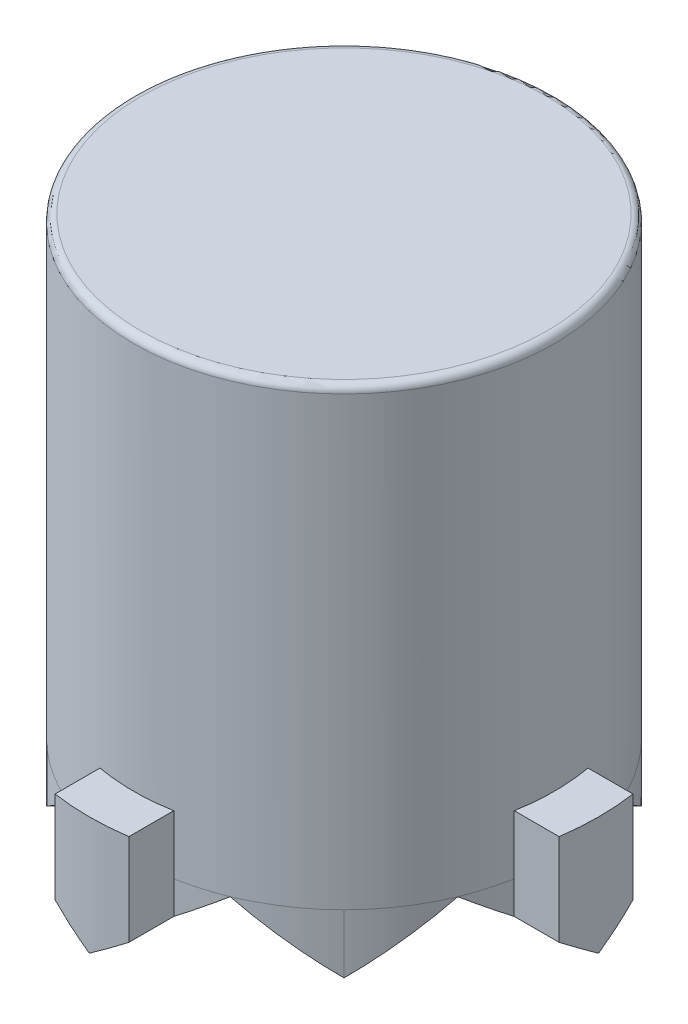
SolidWorks part; units mm, degrees
note: The reader was unsure of these and kept them because the rebuilt part matched: shared geometry of "Croquis22<3>", "Croquis26<2>", "Croquis28<2>", "Croquis29<2>".
ref_plane "Front Plane" through (0, 0, 0) normal (0, 0, 1) x (1, 0, 0)
ref_plane "Top Plane" through (0, 0, 0) normal (0, 1, 0) x (1, 0, 0)
ref_plane "Right Plane" through (0, 0, 0) normal (1, 0, 0) x (0, 0, -1)
sketch "Croquis1" plane through (0, 0, 0) normal (0, 1, 0) x (1, 0, 0)
  circle A0 centre (0, 0) radius 2.85
  dimension "D1" = 5.7
extrude "Saliente-Extruir1" add sketch "Croquis1" along normal blind 6.95
fillet "Redondeo1" radius 0.1 1 edges at (0, 6.95, 2.85)
sketch "Croquis3" plane through (0, 0, 0) normal (0, -1, 0) x (1, 0, 0)
  circle A0 centre (0, 0) radius 2.25
  dimension "D1" = 4.5
extrude "Cortar-Extruir1" cut sketch "Croquis3" against normal blind 4
sketch "Croquis4" plane through (0, 0, 0) normal (0, -1, 0) x (1, 0, 0)
  circle A0 centre (0, 0) radius 2.55
  dimension "D1" = 5.1
curve "Hélice/Espiral1" pitch 12.8 height 0.8 turns 0.0625
sketch "Croquis5" plane through (0, 0, 0) normal (0, -1, 0) x (1, 0, 0)
  circle A1 centre (0, 0) radius 2.55
  circle A2 centre (0, 0) radius 2.55
  dimension "D1" = 0
curve "Hélice/Espiral2" pitch 12.8 height 0.8 turns 0.0625
sketch "Croquis6" plane through (0, 0, 0) normal (0, -1, 0) x (1, 0, 0)
  circle A1 centre (0, 0) radius 2.55
  circle A2 centre (0, 0) radius 2.55
  dimension "D1" = 0
curve "Hélice/Espiral3" pitch 12.8 height 0.8 turns 0.0625
sketch "Croquis7" plane through (0, 0, 0) normal (0, -1, 0) x (1, 0, 0)
  circle A1 centre (0, 0) radius 2.55
  circle A2 centre (0, 0) radius 2.55
  dimension "D1" = 0
curve "Hélice/Espiral4" pitch 12.8 height 0.8 turns 0.0625
sketch "Croquis8" plane through (0, 0, 0) normal (0, -1, 0) x (1, 0, 0)
  circle A1 centre (0, 0) radius 2.55
  circle A2 centre (0, 0) radius 2.55
  dimension "D1" = 0
curve "Hélice/Espiral5" pitch 12.8 height 0.8 turns 0.0625
sketch "Croquis9" plane through (0, 0, 0) normal (0, -1, 0) x (1, 0, 0)
  circle A1 centre (0, 0) radius 2.55
  circle A2 centre (0, 0) radius 2.55
  dimension "D1" = 0
curve "Hélice/Espiral6" pitch 12.8 height 0.8 turns 0.0625
sketch "Croquis10" plane through (0, 0, 0) normal (0, -1, 0) x (1, 0, 0)
  circle A1 centre (0, 0) radius 2.55
  circle A2 centre (0, 0) radius 2.55
  dimension "D1" = 0
curve "Hélice/Espiral7" pitch 12.8 height 0.8 turns 0.0625
sketch "Croquis11" plane through (0, 0, 0) normal (0, -1, 0) x (1, 0, 0)
  circle A1 centre (0, 0) radius 2.55
  circle A2 centre (0, 0) radius 2.55
  dimension "D1" = 0
curve "Hélice/Espiral8" pitch 12.8 height 0.8 turns 0.0625
sketch "Croquis12" plane through (0, 0, 0) normal (0, -1, 0) x (1, 0, 0)
  circle A3 centre (0, 0) radius 2.55
  circle A4 centre (0, 0) radius 2.55
  dimension "D2" = 0
curve "Hélice/Espiral9" pitch 12.8 height 0.8 turns 0.0625
sketch "Croquis13" plane through (0, 0, 0) normal (0, -1, 0) x (1, 0, 0)
  circle A1 centre (0, 0) radius 2.55
  circle A2 centre (0, 0) radius 2.55
  dimension "D1" = 0
curve "Hélice/Espiral10" pitch 12.8 height 0.8 turns 0.0625
sketch "Croquis14" plane through (0, 0, 0) normal (0, -1, 0) x (1, 0, 0)
  circle A1 centre (0, 0) radius 2.55
  circle A2 centre (0, 0) radius 2.55
  dimension "D1" = 0
curve "Hélice/Espiral11" pitch 12.8 height 0.8 turns 0.0625
sketch "Croquis15" plane through (0, 0, 0) normal (0, -1, 0) x (1, 0, 0)
  circle A1 centre (0, 0) radius 2.55
  circle A2 centre (0, 0) radius 2.55
  dimension "D1" = 0
curve "Hélice/Espiral12" pitch 12.8 height 0.8 turns 0.0625
sketch "Croquis16" plane through (0, 0, 0) normal (0, -1, 0) x (1, 0, 0)
  circle A1 centre (0, 0) radius 2.55
  circle A2 centre (0, 0) radius 2.55
  dimension "D1" = 0
curve "Hélice/Espiral13" pitch 12.8 height 0.8 turns 0.0625
sketch "Croquis17" plane through (0, 0, 0) normal (0, -1, 0) x (1, 0, 0)
  circle A1 centre (0, 0) radius 2.55
  circle A2 centre (0, 0) radius 2.55
  dimension "D1" = 0
curve "Hélice/Espiral15" pitch 12.8 height 0.8 turns 0.0625
sketch "Croquis18" plane through (0, 0, 0) normal (0, -1, 0) x (1, 0, 0)
  circle A1 centre (0, 0) radius 2.55
  circle A2 centre (0, 0) radius 2.55
  dimension "D1" = 0
curve "Hélice/Espiral16" pitch 12.8 height 0.8 turns 0.0625
sketch "Croquis19" plane through (0, 0, 0) normal (0, -1, 0) x (1, 0, 0)
  circle A1 centre (0, 0) radius 2.55
  circle A2 centre (0, 0) radius 2.55
  dimension "D1" = 0
curve "Hélice/Espiral17" pitch 12.8 height 0.8 turns 0.0625
sketch "Croquis20" plane through (0, 0, 0) normal (0, -1, 0) x (1, 0, 0)
  circle A1 centre (0, 0) radius 2.85
  circle A2 centre (0, 0) radius 2.85
  dimension "D1" = 0
extrude "Cortar-Extruir2" cut sketch "Croquis20" against normal blind 0.8
curve "CurvaComp2"
sketch "Croquis22" plane through (0, 0, 0) normal (0, 0, 1) x (1, 0, 0)
  line L1 (-2.85, 0.8) -> (-2.25, 0.8)
  line L2 (-2.85, 0.8) -> (-2.85, 0)
  line L3 (-2.85, 0) -> (-2.25, 0)
  line L4 (-2.25, 0.8) -> (-2.25, 0)
  line L5 (-2.85, 0.8) -> (2.85, 0.8) construction
  line L7 (2.85, 0.8) -> (2.25, 0.8)
  line L8 (2.85, 0.8) -> (2.85, 0)
  line L9 (2.85, 0) -> (2.25, 0)
  line L10 (2.25, 0.8) -> (2.25, 0)
  dimension "D1" = 0.8
  dimension "D2" = 0.8
sweep "Barrer2" add profiles "Croquis22" path "Hélice/Espiral7"
sweep "Barrer5" add profiles "Croquis22<3>" path "Hélice/Espiral17"
sketch "Croquis22<3>" plane through (0, 0, 0) normal (0, 0, 1) x (1, 0, 0) same geometry as "Croquis22"
sketch "Croquis26" plane through (0, 0, 0) normal (1, 0, 0) x (0, 0, -1)
  line L1 (-2.85, 0.8) -> (-2.25, 0.8)
  line L2 (-2.85, 0.8) -> (-2.85, 0)
  line L3 (-2.85, 0) -> (-2.25, 0)
  line L4 (-2.25, 0.8) -> (-2.25, 0)
  line L5 (2.85, 0.8) -> (2.25, 0.8)
  line L6 (2.85, 0.8) -> (2.85, 0)
  line L7 (2.85, 0) -> (2.25, 0)
  line L8 (2.25, 0.8) -> (2.25, 0)
  dimension "D1" = 0.8
  dimension "D2" = 0.8
sweep "Barrer6" add profiles "Croquis26" path "Hélice/Espiral15"
sweep "Barrer7" add profiles "Croquis26<2>" path "Hélice/Espiral5"
sketch "Croquis26<2>" plane through (0, 0, 0) normal (1, 0, 0) x (0, 0, -1) same geometry as "Croquis26"
ref_plane "Plano2" through (0, 0, 0) normal (0.7071, 0, 0.7071) x (0.7071, 0, -0.7071)
sketch "Croquis28" plane through (0, 0, 0) normal (0.7071, 0, 0.7071) x (0.7071, 0, -0.7071)
  line L1 (-2.85, 0.8) -> (-2.25, 0.8)
  line L2 (-2.85, 0.8) -> (-2.85, 0)
  line L3 (-2.85, 0) -> (-2.25, 0)
  line L4 (-2.25, 0.8) -> (-2.25, 0)
  line L5 (2.85, 0.8) -> (2.25, 0.8)
  line L6 (2.85, 0.8) -> (2.85, 0)
  line L7 (2.85, 0) -> (2.25, 0)
  line L8 (2.25, 0.8) -> (2.25, 0)
  dimension "D1" = 0.8
  dimension "D2" = 0.8
sweep "Barrer8" add profiles "Croquis28" path "Hélice/Espiral6"
sweep "Barrer9" add profiles "Croquis28<2>" path "Hélice/Espiral16"
sketch "Croquis28<2>" plane through (0, 0, 0) normal (0.7071, 0, 0.7071) x (0.7071, 0, -0.7071) same geometry as "Croquis28"
ref_plane "Plano3" through (0, 0, 0) normal (0.7071, 0, -0.7071) x (-0.7071, 0, -0.7071)
sketch "Croquis29" plane through (0, 0, 0) normal (0.7071, 0, -0.7071) x (-0.7071, 0, -0.7071)
  line L1 (-2.85, 0.8) -> (-2.25, 0.8)
  line L2 (-2.85, 0.8) -> (-2.85, 0)
  line L3 (-2.85, 0) -> (-2.25, 0)
  line L4 (-2.25, 0.8) -> (-2.25, 0)
  line L5 (2.85, 0.8) -> (2.25, 0.8)
  line L6 (2.85, 0.8) -> (2.85, 0)
  line L7 (2.85, 0) -> (2.25, 0)
  line L8 (2.25, 0.8) -> (2.25, 0)
  dimension "D1" = 0.8
  dimension "D2" = 0.8
sweep "Barrer10" add profiles "Croquis29" path "Hélice/Espiral13"
sweep "Barrer11" add profiles "Croquis29<2>" path "Hélice/Espiral4"
sketch "Croquis29<2>" plane through (0, 0, 0) normal (0.7071, 0, -0.7071) x (-0.7071, 0, -0.7071) same geometry as "Croquis29"
sketch "Croquis35" plane through (0, 0, 0) normal (0, 1, 0) x (1, 0, 0)
  line L0 (-3.45, 0) -> (-2.85, 0) construction
  line L1 (0, 3.45) -> (0, 2.85) construction
  line L2 (-3.4136, -0.5) -> (-2.8058, -0.5)
  line L3 (-0.5, 3.4136) -> (-0.5, 2.8058)
  line L4 (-3.4136, 0.5) -> (-2.8058, 0.5)
  line L5 (0.5, 3.4136) -> (0.5, 2.8058)
  line L6 (2.8058, 0.5) -> (3.4136, 0.5)
  line L7 (-4.3854, 0.5) -> (3.9161, 0.5) construction
  line L8 (2.85, 0) -> (3.45, 0) construction
  line L9 (-4.3854, 0) -> (3.9161, 0) construction
  line L10 (2.8058, -0.5) -> (3.4136, -0.5)
  line L11 (-4.3854, -0.5) -> (3.9161, -0.5) construction
  line L12 (0.5, 4.3522) -> (0.5, -4.118) construction
  line L13 (0, 4.3522) -> (0, -4.118) construction
  line L14 (-0.5, 4.3522) -> (-0.5, -4.118) construction
  line L20 (-0.5, -2.8058) -> (-0.5, -3.4136)
  line L21 (0, -2.85) -> (0, -3.45) construction
  line L22 (0.5, -2.8058) -> (0.5, -3.4136)
  circle A0 centre (0, 0) radius 2.85 construction
  arc A1 (0.5, 2.8058) -> (-0.5, 2.8058) centre (0, 0) ccw
  arc A2 (0.5, 3.4136) -> (-0.5, 3.4136) centre (0, 0) ccw
  arc A3 (2.8058, -0.5) -> (2.8058, 0.5) centre (0, 0) ccw
  arc A4 (3.4136, -0.5) -> (3.4136, 0.5) centre (0, 0) ccw
  arc A5 (-3.4136, 0.5) -> (-3.4136, -0.5) centre (0, 0) ccw
  arc A6 (-2.8058, 0.5) -> (-2.8058, -0.5) centre (0, 0) ccw
  arc A7 (-0.5, -3.4136) -> (0.5, -3.4136) centre (0, 0) ccw
  arc A8 (-0.5, -2.8058) -> (0.5, -2.8058) centre (0, 0) ccw
  dimension "D3" = 6.9
  dimension "D1" = 0.5
  dimension "D2" = 0.5
extrude "Saliente-Extruir3" add sketch "Croquis35" along normal blind 1.6
sketch "Croquis36" plane through (0, 0, 0) normal (0, 0, 1) x (1, 0, 0)
  line L2 (-0.5, 0) -> (0, 0)
  line L3 (-0.5, 0.3593) -> (-0.5, 0)
  line L4 (-0.5, 0) -> (0, 0)
  line L5 (-0.5, 0.3593) -> (-0.5, 0)
  spline S1 degree 3 poles (-2811.7886, -1045.2486) (41.4357, -13.483) (-18.6156, -4.761) (-11.001, 28.0922) (-2840.5655, -965.0983) knots -79.058844 -79.058844 -79.058844 -79.058844 0.414544 89.122996 89.122996 89.122996 89.122996 only from (0, 0) to (-0.5, 0.3593)
  spline S2 degree 3 poles (0, 0) (-0.0696, 0.0495) (-0.2375, 0.1688) (-0.4031, 0.2889) (-0.5, 0.3593) knots 0 0 0 0 0.414544 1 1 1 1
  dimension "D1" = 0
extrude "Cortar-Extruir7" cut sketch "Croquis36" against normal mid plane 100
sketch "Croquis37" plane through (0, 0, 0) normal (0, 0, 1) x (1, 0, 0)
  line L2 (0, 0) -> (0.5, 0)
  line L3 (0.5, 0) -> (0.5, 0.3593)
  line L4 (0, 0) -> (0.5, 0)
  line L5 (0.5, 0) -> (0.5, 0.3593)
  arc A0 (0, 0) -> (0.5, 0.3593) centre (-24.3036, 34.3504) ccw
  arc A1 (0, 0) -> (0.5, 0.3593) centre (-24.3036, 34.3504) ccw
  dimension "D1" = 0
extrude "Cortar-Extruir8" cut sketch "Croquis37" against normal mid plane 100
sketch "Croquis38" plane through (0, 0, 0) normal (1, 0, 0) x (0, 0, -1)
  line L2 (-0.5, 0.3593) -> (-0.5, 0)
  line L3 (-0.5, 0) -> (0, 0)
  line L4 (-0.5, 0.3593) -> (-0.5, 0)
  line L5 (-0.5, 0) -> (0, 0)
  arc A0 (-0.5, 0.3593) -> (0, 0) centre (24.3036, 34.3504) ccw
  arc A1 (-0.5, 0.3593) -> (0, 0) centre (24.3036, 34.3504) ccw
  dimension "D1" = 0
extrude "Cortar-Extruir9" cut sketch "Croquis38" against normal mid plane 100
sketch "Croquis39" plane through (0, 0, 0) normal (1, 0, 0) x (0, 0, -1)
  line L2 (0.5, 0) -> (0.5, 0.3593)
  line L3 (0, 0) -> (0.5, 0)
  line L4 (0.5, 0) -> (0.5, 0.3593)
  line L5 (0, 0) -> (0.5, 0)
  arc A0 (0, 0) -> (0.5, 0.3593) centre (-24.3036, 34.3504) ccw
  arc A1 (0, 0) -> (0.5, 0.3593) centre (-24.3036, 34.3504) ccw
  dimension "D1" = 0
extrude "Cortar-Extruir10" cut sketch "Croquis39" against normal mid plane 100
